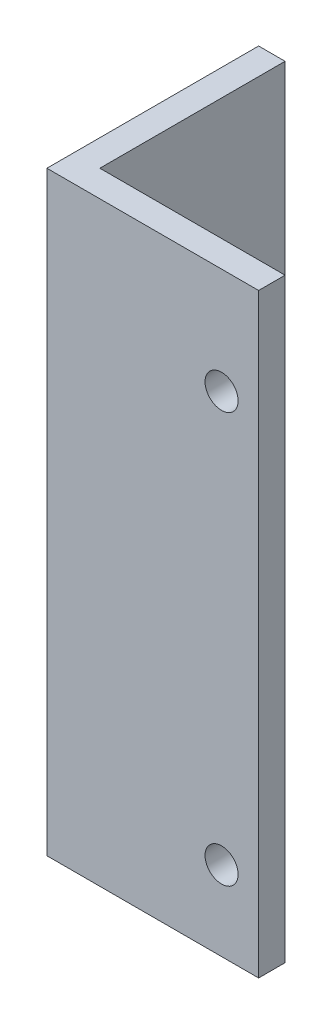
SolidWorks part; units mm, degrees
ref_plane "Front Plane" through (0, 0, 0) normal (0, 0, 1) x (1, 0, 0)
ref_plane "Top Plane" through (0, 0, 0) normal (0, 1, 0) x (1, 0, 0)
ref_plane "Right Plane" through (0, 0, 0) normal (1, 0, 0) x (0, 0, -1)
sketch "Sketch1" plane through (0, 0, 0) normal (0, 1, 0) x (1, 0, 0)
  line L0 (0, 0) -> (16, 0)
  line L1 (16, 0) -> (16, 2)
  line L2 (16, 2) -> (2, 2)
  line L3 (2, 2) -> (2, 16)
  line L4 (2, 16) -> (0, 16)
  line L5 (0, 16) -> (0, 0)
  dimension "D1" = 16
  dimension "D2" = 16
  dimension "D3" = 2
  dimension "D4" = 2
extrude "Boss-Extrude1" add sketch "Sketch1" along normal blind 45
sketch "Sketch2" plane through (0, 0, -2) normal (0, 0, -1) x (-1, 0, 0)
  line L0 (0, 45) -> (0, 0) construction
  line L1 (-16, 45) -> (-2, 45) construction
  circle A0 centre (-13.2, 37) radius 1.25
  circle A1 centre (-13.2, 6) radius 1.25
  dimension "D3" = 2.5
  dimension "D4" = 2.5
  dimension "D1" = 13.2
  dimension "D2" = 31
  dimension "D5" = 8
extrude "Cut-Extrude1" cut sketch "Sketch2" against normal through all
sketch "Sketch3" plane through (2, 0, 0) normal (1, 0, 0) x (0, 0, -1)
  line L0 (2, 0) -> (16, 0) construction
  line L1 (16, 45) -> (16, 0) construction
  circle A0 centre (13, 9.5) radius 1.25
  circle A1 centre (5, 13.5) radius 1.25
  dimension "D2" = 2.5
  dimension "D3" = 2.5
  dimension "D1" = 4
  dimension "D4" = 9.5
  dimension "D5" = 8
  dimension "D6" = 3
extrude "Cut-Extrude2" cut sketch "Sketch3" against normal through all
